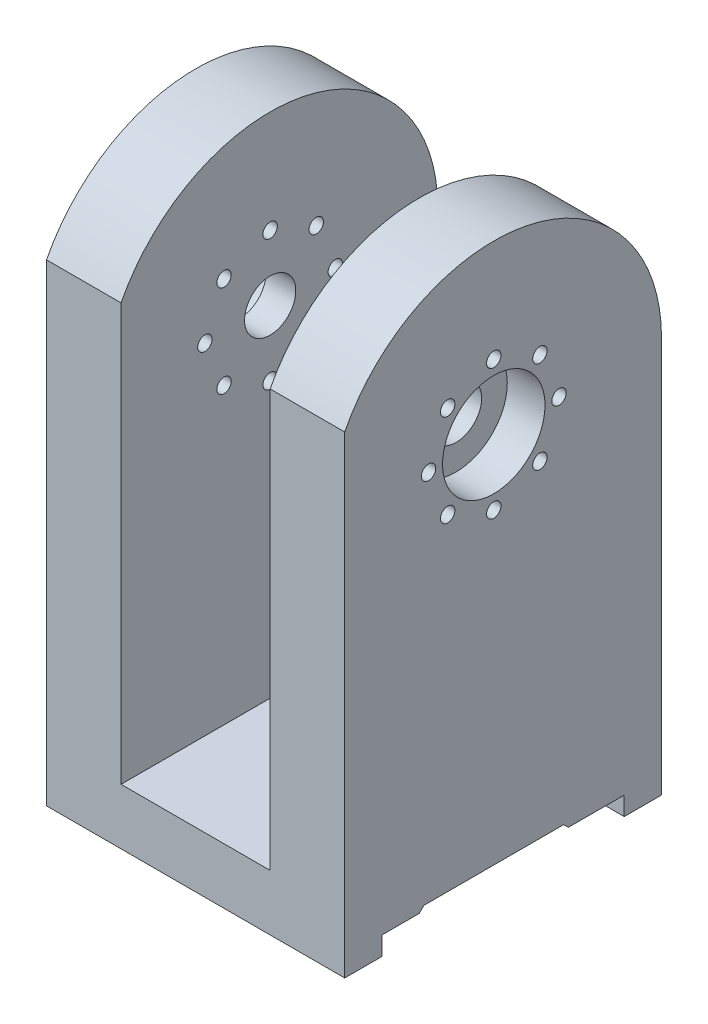
SolidWorks part; units mm, degrees
material "6061 Alloy"
ref_plane "Front Plane" through (0, 0, 0) normal (0, 0, 1) x (1, 0, 0)
ref_plane "Top Plane" through (0, 0, 0) normal (0, 1, 0) x (1, 0, 0)
ref_plane "Right Plane" through (0, 0, 0) normal (1, 0, 0) x (0, 0, -1)
sketch "Sketch1" plane through (0, 0, 0) normal (1, 0, 0) x (0, 0, -1)
  line L2 (107.95, 134.9375) -> (107.95, 0)
  line L3 (107.95, 0) -> (95.25, 0)
  line L4 (95.25, 0) -> (95.25, 6.35)
  line L5 (95.25, 6.35) -> (76.2, 6.35)
  line L6 (76.2, 6.35) -> (74.6125, 7.9375)
  line L7 (74.6125, 7.9375) -> (26.9875, 7.9375)
  line L8 (26.9875, 7.9375) -> (25.4, 6.35)
  line L9 (25.4, 6.35) -> (12.7, 6.35)
  line L10 (12.7, 6.35) -> (12.7, 0)
  line L11 (12.7, 0) -> (0, 0)
  line L12 (0, 0) -> (0, 161.1192)
  line L14 (50.8, 7.9375) -> (50.8, 134.9375) construction
  arc A4 (107.95, 134.9375) -> (0, 161.1192) centre (50.8, 134.9375) ccw
  dimension "D8" = 127
  dimension "D7" = 12.7
  dimension "D1" = 6.35
  dimension "D2" = 1.5875
  dimension "D3" = 12.7
  dimension "D4" = 12.7
  dimension "D5" = 6.35
  dimension "D6" = 19.05
  dimension "D9" = 107.95
extrude "Boss-Extrude1" add sketch "Sketch1" along normal blind 101.6
sketch "Sketch2" plane through (0, 0, -107.95) normal (0, 0, -1) x (-1, 0, 0)
  line L0 (-76.2, 98.425) -> (-76.2, 19.05)
  line L1 (-25.4, 19.05) -> (-25.4, 264.5802)
  line L2 (-76.2, 19.05) -> (-25.4, 19.05)
  line L4 (-101.6, 0) -> (-101.6, 134.9375) construction
  line L5 (-101.6, 0) -> (0, 0) construction
  line L6 (-76.2, 98.425) -> (-76.2, 264.5802)
  line L7 (-76.2, 264.5802) -> (-25.4, 264.5802)
  line L9 (0, 0) -> (0, 134.9375) construction
  dimension "D1" = 25.4
  dimension "D2" = 25.4
  dimension "D3" = 19.05
extrude "Cut-Extrude1" cut sketch "Sketch2" against normal through all and the other way through all contours L2 L0 | L2 L1 L7 L6 L0 region at (50.8, 141.8151, -107.95)
sketch "Sketch5" plane through (0, 0, 0) normal (-1, 0, 0) x (0, 0, 1)
  circle A0 centre (-50.8, 134.9375) radius 17.4625
  arc A1 (0, 161.1192) -> (-107.95, 134.9375) centre (-50.8, 134.9375) ccw construction
  dimension "D1" = 34.925
extrude "Cut-Extrude4" cut sketch "Sketch5" against normal blind 15.24
sketch "Sketch6" plane through (0, 0, 0) normal (-1, 0, 0) x (0, 0, 1)
  circle A0 centre (-50.8, 134.9375) radius 8.7312
  arc A1 (0, 161.1192) -> (-107.95, 134.9375) centre (-50.8, 134.9375) ccw construction
  dimension "D1" = 17.4625
extrude "Cut-Extrude5" cut sketch "Sketch6" against normal through all both and the other way through all
sketch "Sketch7" plane through (101.6, 0, 0) normal (1, 0, 0) x (0, 0, -1)
  circle A0 centre (50.8, 134.9375) radius 17.4625
  arc A1 (107.95, 134.9375) -> (0, 161.1192) centre (50.8, 134.9375) ccw construction
  dimension "D1" = 34.925
extrude "Cut-Extrude6" cut sketch "Sketch7" against normal up to surface (12.8587 mm away)
ref_plane "Plane1" through (50.8, 0, 0) normal (-1, 0, 0) x (0, 0, 1)
hole_wizard "1/4-20 Tapped Hole1" positions "Sketch10" profile "Sketch11" tap size "1/4-20" standard "ANSI Inch"
sketch "Sketch10" plane through (0, 0, 0) normal (0, -1, 0) x (-1, 0, 0)
  point P0 (-19.05, 6.35)
  point P3 (-82.55, 6.35)
  point P6 (-82.55, 101.6)
  point P9 (-19.05, 101.6)
sketch "Sketch11" plane through (19.05, 0, -6.35) normal (1, 0, 0) x (0, 0, -1)
  line L0 (0, 0) -> (0, 18.0438)
  line L1 (0, 18.0438) -> (2.5527, 16.51)
  line L2 (2.5527, 16.51) -> (2.5527, 0)
  line L5 (2.5527, 0) -> (0, 0)
  line L10 (0, 18.0438) -> (-2.5527, 16.51) construction
  line L11 (0, -6.35) -> (0, 107.95) construction
  dimension "Tap Drill Dia." = 5.1054
  dimension "Tap Drill Depth" = 16.51
  dimension "Drill Angle" = 118
cosmetic thread "Hole Thread1" parameters "D1"=12.7, "D2"=6.35
cosmetic thread "Hole Thread2" parameters "D1"=12.7, "D2"=6.35
cosmetic thread "Hole Thread3" parameters "D1"=12.7, "D2"=6.35
cosmetic thread "Hole Thread4" parameters "D1"=12.7, "D2"=6.35
hole_wizard "#10-24 Tapped Hole1" positions "Sketch12" profile "Sketch13" tap size "#10-24" standard "ANSI Inch"
sketch "Sketch12" plane through (0, 0, -107.95) normal (0, 0, -1) x (-1, 0, 0)
  line L0 (-101.6, 0) -> (0, 0) construction
  line L1 (-101.6, 0) -> (-101.6, 134.9375) construction
  line L2 (0, 0) -> (0, 134.9375) construction
  point P0 (-71.12, 3.175)
  point P2 (-30.48, 3.175)
  dimension "D1" = 3.175
  dimension "D2" = 3.175
  dimension "D3" = 30.48
  dimension "D4" = 30.48
sketch "Sketch13" plane through (71.12, 3.175, -107.95) normal (1, 0, 0) x (0, 1, 0)
  line L0 (0, 0) -> (0, 16.0887)
  line L1 (0, 16.0887) -> (1.8986, 14.9479)
  line L2 (1.8986, 14.9479) -> (1.8986, 0)
  line L5 (1.8986, 0) -> (0, 0)
  line L10 (0, 16.0887) -> (-1.8987, 14.9479) construction
  line L11 (0, -6.35) -> (0, 107.95) construction
  dimension "Tap Drill Dia." = 3.7973
  dimension "Tap Drill Depth" = 14.9479
  dimension "Drill Angle" = 118
cosmetic thread "Hole Thread5" parameters "D1"=9.652, "D2"=4.826
cosmetic thread "Hole Thread6" parameters "D1"=9.652, "D2"=4.826
hole_wizard "1/4 (0.25) Diameter Hole1" positions "Sketch14" profile "Sketch15" hole size "1/4" standard "ANSI Inch" end condition through all
sketch "Sketch14" plane through (0, 19.05, 0) normal (0, 1, 0) x (1, 0, 0)
  point P0 (38.1, 50.8)
sketch "Sketch15" plane through (38.1, 19.05, -50.8) normal (1, 0, 0) x (0, 0, 1)
  line L0 (0, 0) -> (0, 19.05)
  line L1 (0, 19.05) -> (3.175, 19.05)
  line L2 (3.175, 19.05) -> (3.175, 0)
  line L5 (3.175, 0) -> (0, 0)
  line L11 (0, -6.35) -> (0, 107.95) construction
  dimension "Thru Hole Dia." = 6.35
  dimension "Thru Hole Depth" = 19.05
hole_wizard "#10 (0.1935) Diameter Hole1" positions "Sketch16" profile "Sketch17" hole size "#10" standard "ANSI Inch" end condition through all
sketch "Sketch16" plane through (0, 0, 0) normal (-1, 0, 0) x (0, 0, 1)
  point P0 (-66.5154, 119.2221)
  point P3 (-50.8, 112.7125)
  point P6 (-35.0846, 119.2221)
  point P9 (-28.575, 134.9375)
  point P12 (-35.0846, 150.6529)
  point P15 (-50.8, 157.1625)
  point P18 (-66.5154, 150.6529)
  point P21 (-73.025, 134.9375)
sketch "Sketch17" plane through (0, 119.2221, -66.5154) normal (0, 1, 0) x (0, 0, 1)
  line L0 (0, 0) -> (0, 101.6)
  line L1 (0, 101.6) -> (2.4574, 101.6)
  line L2 (2.4574, 101.6) -> (2.4574, 0)
  line L5 (2.4574, 0) -> (0, 0)
  line L11 (0, -6.35) -> (0, 107.95) construction
  dimension "Thru Hole Dia." = 4.9149
  dimension "Thru Hole Depth" = 101.6
